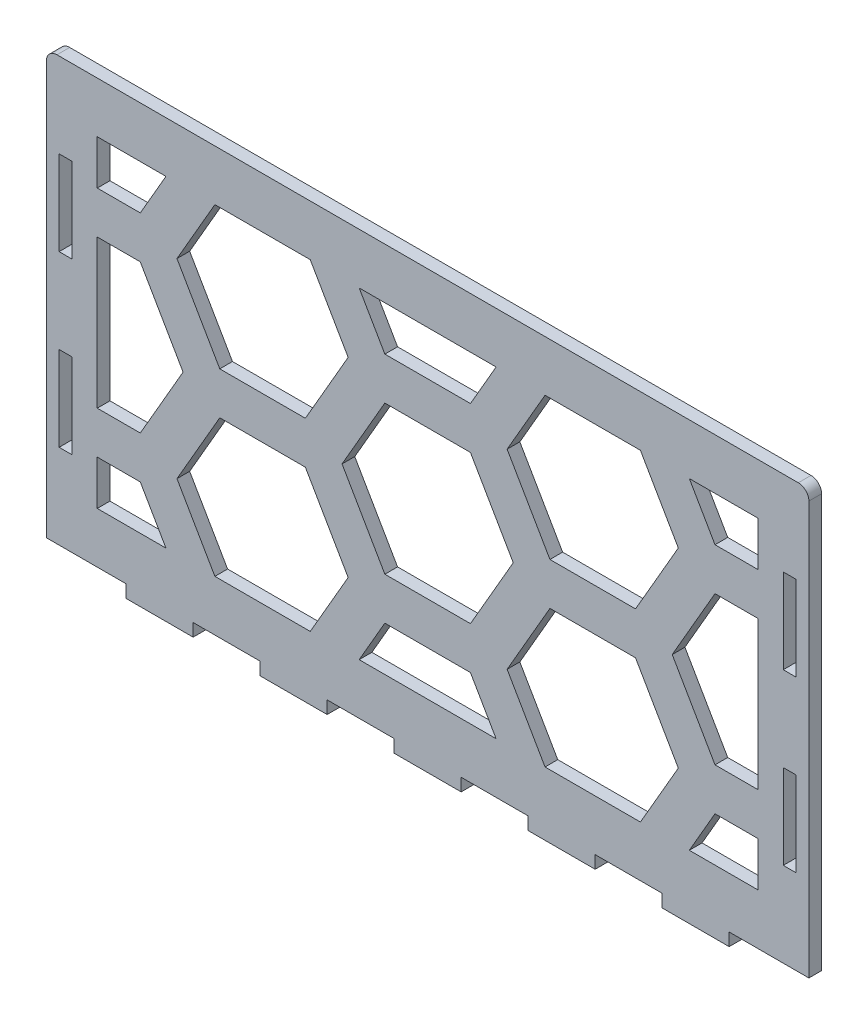
SolidWorks part; units mm, degrees
ref_plane "Front Plane" through (0, 0, 0) normal (0, 0, 1) x (1, 0, 0)
ref_plane "Top Plane" through (0, 0, 0) normal (0, 1, 0) x (1, 0, 0)
ref_plane "Right Plane" through (0, 0, 0) normal (1, 0, 0) x (0, 0, -1)
sketch "Sketch1" plane through (0, 0, 0) normal (0, 0, 1) x (1, 0, 0)
  line L0 (-87, -50) -> (-87, 50) construction
  line L1 (-90, -50) -> (90, -50)
  line L2 (-90, -50) -> (-90, 50)
  line L3 (-90, 50) -> (90, 50)
  line L4 (90, -50) -> (90, 50)
  line L5 (-90, -50) -> (90, 50) construction
  line L6 (-90, 50) -> (90, -50) construction
  line L7 (87, -50) -> (87, 50) construction
  line L8 (-55.3636, -53) -> (-39.5455, -53) construction
  line L9 (-7.9091, -53) -> (7.9091, -53)
  line L10 (-7.9091, -53) -> (-7.9091, -50)
  line L11 (-7.9091, -50) -> (7.9091, -50)
  line L12 (7.9091, -53) -> (7.9091, -50)
  line L13 (-7.9091, -53) -> (7.9091, -50) construction
  line L14 (-7.9091, -50) -> (7.9091, -53) construction
  line L15 (23.7273, -53) -> (39.5455, -53)
  line L16 (23.7273, -53) -> (23.7273, -50)
  line L17 (23.7273, -50) -> (39.5455, -50)
  line L18 (39.5455, -53) -> (39.5455, -50)
  line L19 (23.7273, -53) -> (39.5455, -50) construction
  line L20 (23.7273, -50) -> (39.5455, -53) construction
  line L21 (55.3636, -53) -> (71.1818, -53)
  line L22 (55.3636, -53) -> (55.3636, -50)
  line L23 (55.3636, -50) -> (71.1818, -50)
  line L24 (71.1818, -53) -> (71.1818, -50)
  line L25 (55.3636, -53) -> (71.1818, -50) construction
  line L26 (55.3636, -50) -> (71.1818, -53) construction
  line L27 (-39.5455, -53) -> (-23.7273, -53)
  line L28 (-39.5455, -53) -> (-39.5455, -50)
  line L29 (-39.5455, -50) -> (-23.7273, -50)
  line L30 (-23.7273, -53) -> (-23.7273, -50)
  line L31 (-39.5455, -53) -> (-23.7273, -50) construction
  line L32 (-39.5455, -50) -> (-23.7273, -53) construction
  line L33 (-71.1818, -53) -> (-55.3636, -53)
  line L34 (-71.1818, -53) -> (-71.1818, -50)
  line L35 (-71.1818, -50) -> (-55.3636, -50)
  line L36 (-55.3636, -53) -> (-55.3636, -50)
  line L37 (-71.1818, -53) -> (-55.3636, -50) construction
  line L38 (-71.1818, -50) -> (-55.3636, -53) construction
  line L39 (-23.7273, -53) -> (-7.9091, -53) construction
  line L40 (7.9091, -53) -> (23.7273, -53) construction
  line L41 (39.5455, -53) -> (55.3636, -53) construction
  line L42 (71.1818, -53) -> (87, -53) construction
  line L43 (-71.1818, -53) -> (-87, -53) construction
  line L45 (83.95, 30) -> (87, 30)
  line L46 (83.95, 30) -> (83.95, 10)
  line L47 (83.95, 10) -> (87, 10)
  line L48 (87, 30) -> (87, 10)
  line L49 (83.95, 30) -> (87, 10) construction
  line L50 (83.95, 10) -> (87, 30) construction
  line L63 (83.95, -10) -> (87, -10)
  line L64 (83.95, -10) -> (83.95, -30)
  line L65 (83.95, -30) -> (87, -30)
  line L66 (87, -10) -> (87, -30)
  line L67 (83.95, -10) -> (87, -30) construction
  line L68 (83.95, -30) -> (87, -10) construction
  line L70 (83.95, 50) -> (83.95, 30) construction
  line L71 (83.95, 10) -> (83.95, -10) construction
  line L72 (83.95, -30) -> (83.95, -50) construction
  line L73 (0, -781.5075) -> (0, 49218.4925) construction
  line L82 (-83.95, 10) -> (-87, 10)
  line L83 (-87, 30) -> (-87, 10)
  line L84 (-83.95, 30) -> (-87, 30)
  line L85 (-83.95, 30) -> (-83.95, 10)
  line L86 (-83.95, -30) -> (-87, -30)
  line L87 (-87, -10) -> (-87, -30)
  line L88 (-83.95, -10) -> (-87, -10)
  line L89 (-83.95, -10) -> (-83.95, -30)
  point P0 (0, 0)
  point P10 (0, -51.5)
  point P15 (31.6364, -51.5)
  point P20 (63.2727, -51.5)
  point P25 (-31.6364, -51.5)
  point P30 (-63.2727, -51.5)
  point P39 (85.475, 20)
  point P52 (85.475, -20)
  dimension "D1" = 180
  dimension "D2" = 100
  dimension "D5" = 3
  dimension "D6" = 3.05
  dimension "D3" = 3
  dimension "D4" = 3
extrude "Boss-Extrude1" add sketch "Sketch1" along normal blind 3 contours L1 L4 L3 L2 L45 L48 L47 L46 L63 L66 L65 L64 L84 L85 L82 L83 L88 | L33 L36 L1 L34 | L27 L30 L1 L28 | L9 L12 L1 L10 | L15 L18 L1 L16 | L24 L23 L22 L21 region at (0, 0, 0) region at (-63.2727, -51.5, 0) region at (-31.6364, -51.5, 0) region at (0, -51.5, 0) region at (31.6364, -51.5, 0)
fillet "Fillet3" radius 2.5 2 edges at (90, 50, 1.5) (-90, 50, 1.5)
sketch "Sketch6" plane through (0, 0, 0) normal (0, 0, 1) x (1, 0, 0)
  line L0 (-145.7809, 17.5) -> (-165.9882, 17.5)
  line L1 (-145.7809, -27.5) -> (-165.9882, -27.5)
  line L2 (-165.9882, -27.5) -> (-176.0918, -45)
  line L3 (-176.0918, -45) -> (-165.9882, -62.5)
  line L4 (-165.9882, -62.5) -> (-145.7809, -62.5)
  line L5 (-145.7809, -62.5) -> (-135.6773, -45)
  line L6 (-135.6773, -45) -> (-145.7809, -27.5)
  line L13 (-165.9882, 17.5) -> (-176.0918, 0)
  line L14 (-137.1207, -67.5) -> (-127.0171, -85)
  line L15 (-127.0171, -85) -> (-106.8098, -85)
  line L16 (-106.8098, -85) -> (-96.7062, -67.5)
  line L17 (-96.7062, -67.5) -> (-106.8098, -50)
  line L18 (-106.8098, -50) -> (-127.0171, -50)
  line L19 (-127.0171, -50) -> (-137.1207, -67.5)
  line L20 (-176.0918, 0) -> (-165.9882, -17.5)
  line L21 (-165.9882, -17.5) -> (-145.7809, -17.5)
  line L22 (-145.7809, -17.5) -> (-135.6773, 0)
  line L23 (-135.6773, 0) -> (-145.7809, 17.5)
  line L24 (-137.1207, -22.5) -> (-127.0171, -40)
  line L25 (-127.0171, -40) -> (-106.8098, -40)
  line L26 (-106.8098, -40) -> (-96.7062, -22.5)
  line L27 (-96.7062, -22.5) -> (-106.8098, -5)
  line L28 (-106.8098, -5) -> (-127.0171, -5)
  line L29 (-127.0171, -5) -> (-137.1207, -22.5)
  line L30 (-145.7809, 62.5) -> (-165.9882, 62.5)
  line L31 (-165.9882, 62.5) -> (-176.0918, 45)
  line L32 (-176.0918, 45) -> (-165.9882, 27.5)
  line L33 (-165.9882, 27.5) -> (-145.7809, 27.5)
  line L34 (-145.7809, 27.5) -> (-135.6773, 45)
  line L35 (-135.6773, 45) -> (-145.7809, 62.5)
  line L36 (-137.1207, 22.5) -> (-127.0171, 5)
  line L37 (-127.0171, 5) -> (-106.8098, 5)
  line L38 (-106.8098, 5) -> (-96.7062, 22.5)
  line L39 (-96.7062, 22.5) -> (-106.8098, 40)
  line L40 (-106.8098, 40) -> (-127.0171, 40)
  line L41 (-127.0171, 40) -> (-137.1207, 22.5)
  line L42 (-145.7809, 107.5) -> (-165.9882, 107.5)
  line L43 (-165.9882, 107.5) -> (-176.0918, 90)
  line L44 (-176.0918, 90) -> (-165.9882, 72.5)
  line L45 (-165.9882, 72.5) -> (-145.7809, 72.5)
  line L46 (-145.7809, 72.5) -> (-135.6773, 90)
  line L47 (-135.6773, 90) -> (-145.7809, 107.5)
  line L48 (-137.1207, 67.5) -> (-127.0171, 50)
  line L49 (-127.0171, 50) -> (-106.8098, 50)
  line L50 (-106.8098, 50) -> (-96.7062, 67.5)
  line L51 (-96.7062, 67.5) -> (-106.8098, 85)
  line L52 (-106.8098, 85) -> (-127.0171, 85)
  line L53 (-127.0171, 85) -> (-137.1207, 67.5)
  line L54 (-145.7809, 152.5) -> (-165.9882, 152.5)
  line L55 (-165.9882, 152.5) -> (-176.0918, 135)
  line L56 (-176.0918, 135) -> (-165.9882, 117.5)
  line L57 (-165.9882, 117.5) -> (-145.7809, 117.5)
  line L58 (-145.7809, 117.5) -> (-135.6773, 135)
  line L59 (-135.6773, 135) -> (-145.7809, 152.5)
  line L60 (-137.1207, 112.5) -> (-127.0171, 95)
  line L61 (-127.0171, 95) -> (-106.8098, 95)
  line L62 (-106.8098, 95) -> (-96.7062, 112.5)
  line L63 (-96.7062, 112.5) -> (-106.8098, 130)
  line L64 (-106.8098, 130) -> (-127.0171, 130)
  line L65 (-127.0171, 130) -> (-137.1207, 112.5)
  line L66 (-145.7809, 197.5) -> (-165.9882, 197.5)
  line L67 (-165.9882, 197.5) -> (-176.0918, 180)
  line L68 (-176.0918, 180) -> (-165.9882, 162.5)
  line L69 (-165.9882, 162.5) -> (-145.7809, 162.5)
  line L70 (-145.7809, 162.5) -> (-135.6773, 180)
  line L71 (-135.6773, 180) -> (-145.7809, 197.5)
  line L72 (-137.1207, 157.5) -> (-127.0171, 140)
  line L73 (-127.0171, 140) -> (-106.8098, 140)
  line L74 (-106.8098, 140) -> (-96.7062, 157.5)
  line L75 (-96.7062, 157.5) -> (-106.8098, 175)
  line L76 (-106.8098, 175) -> (-127.0171, 175)
  line L77 (-127.0171, 175) -> (-137.1207, 157.5)
  line L102 (-145.7809, -27.5) -> (-145.7809, 17.5) construction
  line L103 (-127.0171, -50) -> (-127.0171, -40) construction
  line L104 (-140.7291, -36.25) -> (-132.0689, -31.25) construction
  line L105 (-59.1784, 157.5) -> (-49.0748, 140)
  line L106 (-49.0748, 140) -> (-28.8675, 140)
  line L107 (-28.8675, 140) -> (-18.7639, 157.5)
  line L108 (-18.7639, 157.5) -> (-28.8675, 175)
  line L109 (-28.8675, 175) -> (-49.0748, 175)
  line L110 (-49.0748, 175) -> (-59.1784, 157.5)
  line L111 (-67.8387, 197.5) -> (-88.0459, 197.5)
  line L112 (-88.0459, 197.5) -> (-98.1495, 180)
  line L113 (-98.1495, 180) -> (-88.0459, 162.5)
  line L114 (-88.0459, 162.5) -> (-67.8387, 162.5)
  line L115 (-67.8387, 162.5) -> (-57.735, 180)
  line L116 (-57.735, 180) -> (-67.8387, 197.5)
  line L117 (-67.8387, 152.5) -> (-88.0459, 152.5)
  line L118 (-88.0459, 152.5) -> (-98.1495, 135)
  line L119 (-98.1495, 135) -> (-88.0459, 117.5)
  line L120 (-88.0459, 117.5) -> (-67.8387, 117.5)
  line L121 (-67.8387, 117.5) -> (-57.735, 135)
  line L122 (-57.735, 135) -> (-67.8387, 152.5)
  line L123 (-67.8387, 107.5) -> (-88.0459, 107.5)
  line L124 (-88.0459, 107.5) -> (-98.1495, 90)
  line L125 (-98.1495, 90) -> (-88.0459, 72.5)
  line L126 (-88.0459, 72.5) -> (-67.8387, 72.5)
  line L127 (-67.8387, 72.5) -> (-57.735, 90)
  line L128 (-57.735, 90) -> (-67.8387, 107.5)
  line L129 (-67.8387, 62.5) -> (-88.0459, 62.5)
  line L130 (-88.0459, 62.5) -> (-98.1495, 45)
  line L131 (-98.1495, 45) -> (-88.0459, 27.5)
  line L132 (-88.0459, 27.5) -> (-67.8387, 27.5)
  line L133 (-67.8387, 27.5) -> (-57.735, 45)
  line L134 (-57.735, 45) -> (-67.8387, 62.5)
  line L135 (-59.1784, 22.5) -> (-49.0748, 5)
  line L136 (-49.0748, 5) -> (-28.8675, 5)
  line L137 (-28.8675, 5) -> (-18.7639, 22.5)
  line L138 (-18.7639, 22.5) -> (-28.8675, 40)
  line L139 (-28.8675, 40) -> (-49.0748, 40)
  line L140 (-49.0748, 40) -> (-59.1784, 22.5)
  line L141 (-67.8387, 17.5) -> (-88.0459, 17.5)
  line L142 (-88.0459, 17.5) -> (-98.1495, 0)
  line L143 (-98.1495, 0) -> (-88.0459, -17.5)
  line L144 (-88.0459, -17.5) -> (-67.8387, -17.5)
  line L145 (-67.8387, -17.5) -> (-57.735, 0)
  line L146 (-57.735, 0) -> (-67.8387, 17.5)
  line L147 (-59.1784, -22.5) -> (-49.0748, -40)
  line L148 (-49.0748, -40) -> (-28.8675, -40)
  line L149 (-28.8675, -40) -> (-18.7639, -22.5)
  line L150 (-18.7639, -22.5) -> (-28.8675, -5)
  line L151 (-28.8675, -5) -> (-49.0748, -5)
  line L152 (-49.0748, -5) -> (-59.1784, -22.5)
  line L153 (-67.8387, -27.5) -> (-88.0459, -27.5)
  line L154 (-88.0459, -27.5) -> (-98.1495, -45)
  line L155 (-98.1495, -45) -> (-88.0459, -62.5)
  line L156 (-88.0459, -62.5) -> (-67.8387, -62.5)
  line L157 (-67.8387, -62.5) -> (-57.735, -45)
  line L158 (-57.735, -45) -> (-67.8387, -27.5)
  line L159 (-59.1784, -67.5) -> (-49.0748, -85)
  line L160 (-49.0748, -85) -> (-28.8675, -85)
  line L161 (-28.8675, -85) -> (-18.7639, -67.5)
  line L162 (-18.7639, -67.5) -> (-28.8675, -50)
  line L163 (-28.8675, -50) -> (-49.0748, -50)
  line L164 (-49.0748, -50) -> (-59.1784, -67.5)
  line L165 (-59.1784, 67.5) -> (-49.0748, 50)
  line L166 (-49.0748, 50) -> (-28.8675, 50)
  line L167 (-28.8675, 50) -> (-18.7639, 67.5)
  line L168 (-18.7639, 67.5) -> (-28.8675, 85)
  line L169 (-28.8675, 85) -> (-49.0748, 85)
  line L170 (-49.0748, 85) -> (-59.1784, 67.5)
  line L171 (-59.1784, 112.5) -> (-49.0748, 95)
  line L172 (-49.0748, 95) -> (-28.8675, 95)
  line L173 (-28.8675, 95) -> (-18.7639, 112.5)
  line L174 (-18.7639, 112.5) -> (-28.8675, 130)
  line L175 (-28.8675, 130) -> (-49.0748, 130)
  line L176 (-49.0748, 130) -> (-59.1784, 112.5)
  line L177 (18.7639, 157.5) -> (28.8675, 140)
  line L178 (28.8675, 140) -> (49.0748, 140)
  line L179 (49.0748, 140) -> (59.1784, 157.5)
  line L180 (59.1784, 157.5) -> (49.0748, 175)
  line L181 (49.0748, 175) -> (28.8675, 175)
  line L182 (28.8675, 175) -> (18.7639, 157.5)
  line L183 (10.1036, 197.5) -> (-10.1036, 197.5)
  line L184 (-10.1036, 197.5) -> (-20.2073, 180)
  line L185 (-20.2073, 180) -> (-10.1036, 162.5)
  line L186 (-10.1036, 162.5) -> (10.1036, 162.5)
  line L187 (10.1036, 162.5) -> (20.2073, 180)
  line L188 (20.2073, 180) -> (10.1036, 197.5)
  line L189 (10.1036, 152.5) -> (-10.1036, 152.5)
  line L190 (-10.1036, 152.5) -> (-20.2073, 135)
  line L191 (-20.2073, 135) -> (-10.1036, 117.5)
  line L192 (-10.1036, 117.5) -> (10.1036, 117.5)
  line L193 (10.1036, 117.5) -> (20.2073, 135)
  line L194 (20.2073, 135) -> (10.1036, 152.5)
  line L195 (10.1036, 107.5) -> (-10.1036, 107.5)
  line L196 (-10.1036, 107.5) -> (-20.2073, 90)
  line L197 (-20.2073, 90) -> (-10.1036, 72.5)
  line L198 (-10.1036, 72.5) -> (10.1036, 72.5)
  line L199 (10.1036, 72.5) -> (20.2073, 90)
  line L200 (20.2073, 90) -> (10.1036, 107.5)
  line L201 (10.1036, 62.5) -> (-10.1036, 62.5)
  line L202 (-10.1036, 62.5) -> (-20.2073, 45)
  line L203 (-20.2073, 45) -> (-10.1036, 27.5)
  line L204 (-10.1036, 27.5) -> (10.1036, 27.5)
  line L205 (10.1036, 27.5) -> (20.2073, 45)
  line L206 (20.2073, 45) -> (10.1036, 62.5)
  line L207 (18.7639, 22.5) -> (28.8675, 5)
  line L208 (28.8675, 5) -> (49.0748, 5)
  line L209 (49.0748, 5) -> (59.1784, 22.5)
  line L210 (59.1784, 22.5) -> (49.0748, 40)
  line L211 (49.0748, 40) -> (28.8675, 40)
  line L212 (28.8675, 40) -> (18.7639, 22.5)
  line L213 (10.1036, 17.5) -> (-10.1036, 17.5)
  line L214 (-10.1036, 17.5) -> (-20.2073, 0)
  line L215 (-20.2073, 0) -> (-10.1036, -17.5)
  line L216 (-10.1036, -17.5) -> (10.1036, -17.5)
  line L217 (10.1036, -17.5) -> (20.2073, 0)
  line L218 (20.2073, 0) -> (10.1036, 17.5)
  line L219 (18.7639, -22.5) -> (28.8675, -40)
  line L220 (28.8675, -40) -> (49.0748, -40)
  line L221 (49.0748, -40) -> (59.1784, -22.5)
  line L222 (59.1784, -22.5) -> (49.0748, -5)
  line L223 (49.0748, -5) -> (28.8675, -5)
  line L224 (28.8675, -5) -> (18.7639, -22.5)
  line L225 (10.1036, -27.5) -> (-10.1036, -27.5)
  line L226 (-10.1036, -27.5) -> (-20.2073, -45)
  line L227 (-20.2073, -45) -> (-10.1036, -62.5)
  line L228 (-10.1036, -62.5) -> (10.1036, -62.5)
  line L229 (10.1036, -62.5) -> (20.2073, -45)
  line L230 (20.2073, -45) -> (10.1036, -27.5)
  line L231 (18.7639, -67.5) -> (28.8675, -85)
  line L232 (28.8675, -85) -> (49.0748, -85)
  line L233 (49.0748, -85) -> (59.1784, -67.5)
  line L234 (59.1784, -67.5) -> (49.0748, -50)
  line L235 (49.0748, -50) -> (28.8675, -50)
  line L236 (28.8675, -50) -> (18.7639, -67.5)
  line L237 (18.7639, 67.5) -> (28.8675, 50)
  line L238 (28.8675, 50) -> (49.0748, 50)
  line L239 (49.0748, 50) -> (59.1784, 67.5)
  line L240 (59.1784, 67.5) -> (49.0748, 85)
  line L241 (49.0748, 85) -> (28.8675, 85)
  line L242 (28.8675, 85) -> (18.7639, 67.5)
  line L243 (18.7639, 112.5) -> (28.8675, 95)
  line L244 (28.8675, 95) -> (49.0748, 95)
  line L245 (49.0748, 95) -> (59.1784, 112.5)
  line L246 (59.1784, 112.5) -> (49.0748, 130)
  line L247 (49.0748, 130) -> (28.8675, 130)
  line L248 (28.8675, 130) -> (18.7639, 112.5)
  line L249 (96.7062, 157.5) -> (106.8098, 140)
  line L250 (106.8098, 140) -> (127.0171, 140)
  line L251 (127.0171, 140) -> (137.1207, 157.5)
  line L252 (137.1207, 157.5) -> (127.0171, 175)
  line L253 (127.0171, 175) -> (106.8098, 175)
  line L254 (106.8098, 175) -> (96.7062, 157.5)
  line L255 (88.0459, 197.5) -> (67.8387, 197.5)
  line L256 (67.8387, 197.5) -> (57.735, 180)
  line L257 (57.735, 180) -> (67.8387, 162.5)
  line L258 (67.8387, 162.5) -> (88.0459, 162.5)
  line L259 (88.0459, 162.5) -> (98.1495, 180)
  line L260 (98.1495, 180) -> (88.0459, 197.5)
  line L261 (88.0459, 152.5) -> (67.8387, 152.5)
  line L262 (67.8387, 152.5) -> (57.735, 135)
  line L263 (57.735, 135) -> (67.8387, 117.5)
  line L264 (67.8387, 117.5) -> (88.0459, 117.5)
  line L265 (88.0459, 117.5) -> (98.1495, 135)
  line L266 (98.1495, 135) -> (88.0459, 152.5)
  line L267 (88.0459, 107.5) -> (67.8387, 107.5)
  line L268 (67.8387, 107.5) -> (57.735, 90)
  line L269 (57.735, 90) -> (67.8387, 72.5)
  line L270 (67.8387, 72.5) -> (88.0459, 72.5)
  line L271 (88.0459, 72.5) -> (98.1495, 90)
  line L272 (98.1495, 90) -> (88.0459, 107.5)
  line L273 (88.0459, 62.5) -> (67.8387, 62.5)
  line L274 (67.8387, 62.5) -> (57.735, 45)
  line L275 (57.735, 45) -> (67.8387, 27.5)
  line L276 (67.8387, 27.5) -> (88.0459, 27.5)
  line L277 (88.0459, 27.5) -> (98.1495, 45)
  line L278 (98.1495, 45) -> (88.0459, 62.5)
  line L279 (96.7062, 22.5) -> (106.8098, 5)
  line L280 (106.8098, 5) -> (127.0171, 5)
  line L281 (127.0171, 5) -> (137.1207, 22.5)
  line L282 (137.1207, 22.5) -> (127.0171, 40)
  line L283 (127.0171, 40) -> (106.8098, 40)
  line L284 (106.8098, 40) -> (96.7062, 22.5)
  line L285 (88.0459, 17.5) -> (67.8387, 17.5)
  line L286 (67.8387, 17.5) -> (57.735, 0)
  line L287 (57.735, 0) -> (67.8387, -17.5)
  line L288 (67.8387, -17.5) -> (88.0459, -17.5)
  line L289 (88.0459, -17.5) -> (98.1495, 0)
  line L290 (98.1495, 0) -> (88.0459, 17.5)
  line L291 (96.7062, -22.5) -> (106.8098, -40)
  line L292 (106.8098, -40) -> (127.0171, -40)
  line L293 (127.0171, -40) -> (137.1207, -22.5)
  line L294 (137.1207, -22.5) -> (127.0171, -5)
  line L295 (127.0171, -5) -> (106.8098, -5)
  line L296 (106.8098, -5) -> (96.7062, -22.5)
  line L297 (88.0459, -27.5) -> (67.8387, -27.5)
  line L298 (67.8387, -27.5) -> (57.735, -45)
  line L299 (57.735, -45) -> (67.8387, -62.5)
  line L300 (67.8387, -62.5) -> (88.0459, -62.5)
  line L301 (88.0459, -62.5) -> (98.1495, -45)
  line L302 (98.1495, -45) -> (88.0459, -27.5)
  line L303 (96.7062, -67.5) -> (106.8098, -85)
  line L304 (106.8098, -85) -> (127.0171, -85)
  line L305 (127.0171, -85) -> (137.1207, -67.5)
  line L306 (137.1207, -67.5) -> (127.0171, -50)
  line L307 (127.0171, -50) -> (106.8098, -50)
  line L308 (106.8098, -50) -> (96.7062, -67.5)
  line L309 (96.7062, 67.5) -> (106.8098, 50)
  line L310 (106.8098, 50) -> (127.0171, 50)
  line L311 (127.0171, 50) -> (137.1207, 67.5)
  line L312 (137.1207, 67.5) -> (127.0171, 85)
  line L313 (127.0171, 85) -> (106.8098, 85)
  line L314 (106.8098, 85) -> (96.7062, 67.5)
  line L315 (96.7062, 112.5) -> (106.8098, 95)
  line L316 (106.8098, 95) -> (127.0171, 95)
  line L317 (127.0171, 95) -> (137.1207, 112.5)
  line L318 (137.1207, 112.5) -> (127.0171, 130)
  line L319 (127.0171, 130) -> (106.8098, 130)
  line L320 (106.8098, 130) -> (96.7062, 112.5)
  line L321 (-137.1207, 157.5) -> (-59.1784, 157.5) construction
  line L322 (-93.0977, -36.25) -> (-101.758, -31.25) construction
  line L324 (-78, -38) -> (78, -38)
  line L325 (-78, -38) -> (-78, 38)
  line L326 (-78, 38) -> (78, 38)
  line L327 (78, -38) -> (78, 38)
  line L328 (-78, -38) -> (78, 38) construction
  line L329 (-78, 38) -> (78, -38) construction
  line L331 (-106.8098, -5) -> (-78, -5) construction
  line L332 (106.8098, -5) -> (78, -5) construction
  line L336 (90, -50) -> (90, 47.5) construction
  line L337 (7.9091, -50) -> (23.7273, -50) construction
  circle A0 centre (-155.8846, -45) radius 17.5 construction
  circle A1 centre (-116.9134, -67.5) radius 17.5 construction
  point P10 (-127.0171, -45)
  point P301 (0, 0)
  point P306 (78, 0)
  dimension "D3" = 35
  dimension "D2" = 45
  dimension "D5" = 12
  dimension "D7" = 12
  dimension "D1" = 6
  dimension "D4" = 4
extrude "Cut-Extrude8" cut sketch "Sketch6" against normal through all both and the other way through all contours L325 L143 L144 L145 L146 L141 L142 | L325 L131 L132 L133 | L140 L135 L136 L137 L138 | L217 L218 L213 L214 L215 L216 | L212 L207 L208 L209 L210 | L289 L327 L290 L285 L286 L287 L288 | L275 L276 L277 L327 | L203 L204 L205 | L151 L152 L147 L148 L149 L150 | L325 L324 L158 L153 L154 | L226 L324 L230 L225 | L223 L224 L219 L220 L221 L222 | L324 L327 L302 L297 L298 region at (-71.2877, 33.1521, 0) region at (-38.9711, 21.8084, 0) region at (-70.1138, 0, 0) region at (0, 33.1538, 0) region at (-71.2877, -33.1521, 0) region at (38.9711, 21.8084, 0) region at (71.2877, 33.1521, 0) region at (-38.9711, -21.8084, 0) region at (0, -33.1538, 0) region at (70.1138, 0, 0) region at (38.9711, -21.8084, 0) region at (71.2877, -33.1521, 0) region at (0, 0, 0)
equation "\"bottomLength\"= 220mm"
equation "\"topLength\"= 330mm"
equation "\"frontHeight\"= 100mm"
equation "\"height\"= 180mm"
equation "\"width\"= 180mm"
equation "\"D2@Sketch1\"=\"frontHeight\""
equation "\"D1@Sketch1\"=\"width\""
